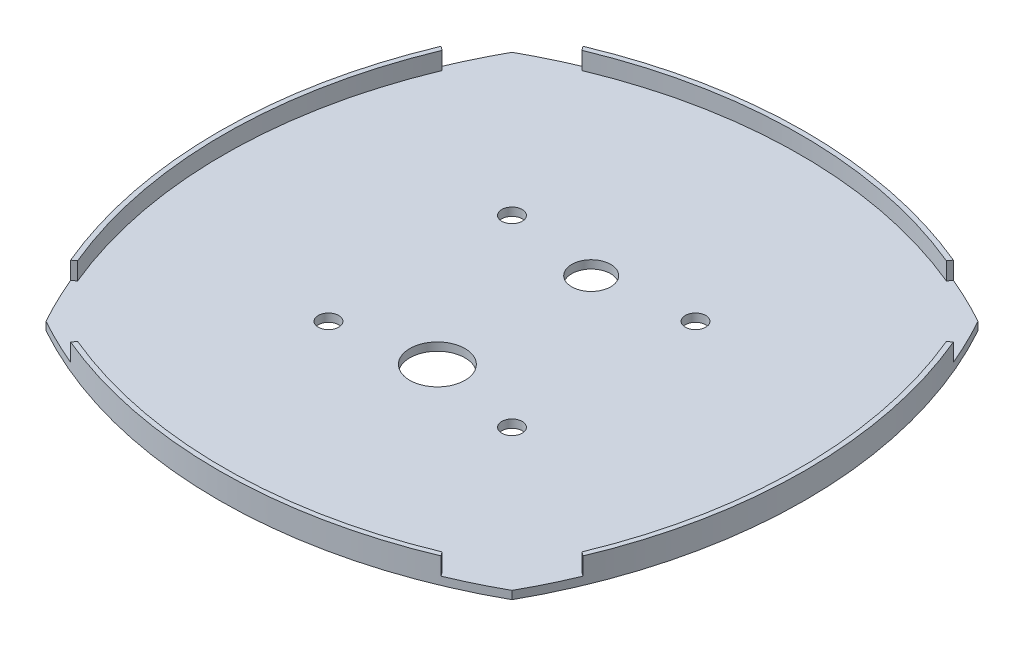
SolidWorks part; units mm, degrees
ref_plane "Front Plane" through (0, 0, 0) normal (0, 0, 1) x (1, 0, 0)
ref_plane "Top Plane" through (0, 0, 0) normal (0, 1, 0) x (1, 0, 0)
ref_plane "Right Plane" through (0, 0, 0) normal (1, 0, 0) x (0, 0, -1)
sketch "Sketch1" plane through (0, 0, 0) normal (0, 1, 0) x (1, 0, 0)
  line L0 (175.429, 389.4302) -> (225.429, 389.4742) construction
  dimension "D1" = 50
sketch "Sketch3" plane through (0, 0, 0) normal (0, 1, 0) x (1, 0, 0)
  line L2 (199.3319, -52.9004) -> (358.0133, -52.9004) construction
  line L3 (199.3319, -52.9004) -> (199.3319, 49.5555) construction
  arc A5 (130.4554, 15.9761) -> (130.4554, -121.7769) centre (256.8431, -52.9004) ccw construction
  arc A6 (268.2084, 15.9761) -> (130.4554, 15.9761) centre (199.3319, -110.4116) ccw construction
  arc A7 (268.2084, -121.7769) -> (268.2084, 15.9761) centre (141.8208, -52.9004) ccw construction
  arc A9 (130.4554, -121.7769) -> (268.2084, -121.7769) centre (199.3319, 4.6107) ccw construction
  arc A12 (271.1535, 18.9212) -> (127.5103, 18.9212) centre (199.3319, -110.4116) ccw
  arc A14 (127.5103, 18.9212) -> (127.5103, -124.722) centre (256.8431, -52.9004) ccw
  arc A15 (127.5103, -124.722) -> (271.1535, -124.722) centre (199.3319, 4.6107) ccw
  arc A16 (271.1535, -124.722) -> (271.1535, 18.9212) centre (141.8208, -52.9004) ccw
  point P0 (199.3319, -52.9004)
  point P15 (199.3319, -52.9004)
  dimension "D1" = 4
extrude "Boss-Extrude1" add sketch "Sketch3" along normal blind 2.5
sketch "Sketch5" plane through (0, 2.5, 0) normal (0, 1, 0) x (1, 0, 0)
  line L0 (141.8208, -52.9004) -> (256.8431, -52.9004) construction
  line L1 (199.3319, 4.6107) -> (199.3319, -110.4116) construction
  line L2 (121.6116, -109.0803) -> (120.3642, -109.9865)
  line L3 (143.1521, -130.6208) -> (142.2458, -131.8681)
  line L4 (277.0523, 3.2794) -> (278.2996, 4.1857)
  line L5 (255.5118, 24.8199) -> (256.418, 26.0673)
  line L6 (277.0523, -109.0803) -> (278.2996, -109.9865)
  line L7 (255.5118, -130.6208) -> (256.418, -131.8681)
  line L8 (121.6125, 3.2817) -> (120.3652, 4.1879)
  line L9 (143.1498, 24.819) -> (142.2436, 26.0663)
  line L10 (110.4063, 20.1528) -> (110.4063, -83.3423) construction
  line L11 (288.2576, 27.2093) -> (288.2576, -79.0531) construction
  line L12 (35.0838, 36.0252) -> (347.5932, 36.0252) construction
  line L13 (32.3242, -141.8261) -> (353.5329, -141.8261) construction
  arc A8 (128.614, -123.6184) -> (270.0499, -123.6184) centre (199.3319, 4.6107) ccw
  arc A9 (270.0499, -123.6184) -> (270.0499, 17.8175) centre (141.8208, -52.9004) ccw
  arc A10 (270.0499, 17.8175) -> (128.614, 17.8175) centre (199.3319, -110.4116) ccw
  arc A11 (128.614, 17.8175) -> (128.614, -123.6184) centre (256.8431, -52.9004) ccw
  arc A12 (143.1521, -130.6208) -> (255.5118, -130.6208) centre (199.3319, 4.6107) ccw
  arc A13 (277.0523, -109.0803) -> (277.0523, 3.2794) centre (141.8208, -52.9004) ccw
  arc A14 (255.5118, 24.8199) -> (143.1498, 24.819) centre (199.3319, -110.4116) ccw
  arc A15 (121.6125, 3.2817) -> (121.6116, -109.0803) centre (256.8431, -52.9004) ccw
  arc A21 (271.1535, 18.9212) -> (127.5103, 18.9212) centre (199.3319, -110.4116) ccw
  arc A22 (271.1535, -124.722) -> (271.1535, 18.9212) centre (141.8208, -52.9004) ccw
  arc A23 (127.5103, -124.722) -> (271.1535, -124.722) centre (199.3319, 4.6107) ccw
  arc A24 (127.5103, 18.9212) -> (127.5103, -124.722) centre (256.8431, -52.9004) ccw
  arc A25 (256.418, 26.0673) -> (142.2436, 26.0663) centre (199.3319, -110.4116) ccw
  arc A26 (278.2996, -109.9865) -> (278.2996, 4.1857) centre (141.8208, -52.9004) ccw
  arc A27 (142.2458, -131.8681) -> (256.418, -131.8681) centre (199.3319, 4.6107) ccw
  arc A28 (120.3652, 4.1879) -> (120.3642, -109.9865) centre (256.8431, -52.9004) ccw
  dimension "D2" = 36
  dimension "D3" = 36
  dimension "D4" = 36
  dimension "D5" = 36
  dimension "D6" = 36
  dimension "D7" = 36
  dimension "D8" = 36
  dimension "D9" = 36
  dimension "D1" = 1.5
  dimension "D10" = 0
extrude "Boss-Extrude2" add sketch "Sketch5" along normal blind 5.4
sketch "Sketch11" plane through (0, 2.5, 0) normal (0, 1, 0) x (1, 0, 0)
  line L0 (127.5103, -124.722) -> (271.1535, 18.9212) construction
  line L1 (127.5103, 18.9212) -> (271.1535, -124.722) construction
  line L2 (199.3319, -50.7415) -> (199.3319, 48.5237) construction
  line L3 (199.3319, -51.4827) -> (293.7423, -51.4827) construction
  line L4 (110.7084, -21.1162) -> (306.7837, -21.1162) construction
  circle A0 centre (171.0477, -24.6162) radius 3.15
  circle A1 centre (227.6162, -24.6162) radius 3.15
  circle A2 centre (227.6162, -81.1847) radius 3.15
  circle A3 centre (171.0477, -81.1847) radius 3.15
  circle A4 centre (199.3319, -75.9004) radius 8.5
  circle A5 centre (199.3319, -28.4827) radius 6
  point P11 (199.3319, -52.9004)
  point P24 (199.3319, -52.9004)
  dimension "D2" = 6.3
  dimension "D4" = 17
  dimension "D7" = 12
  dimension "D3" = 40
  dimension "D5" = 23
  dimension "D6" = 3.5
  dimension "D8" = 23
  dimension "D1" = 4
extrude "Cut-Extrude2" cut sketch "Sketch11" against normal through all both and the other way through all
